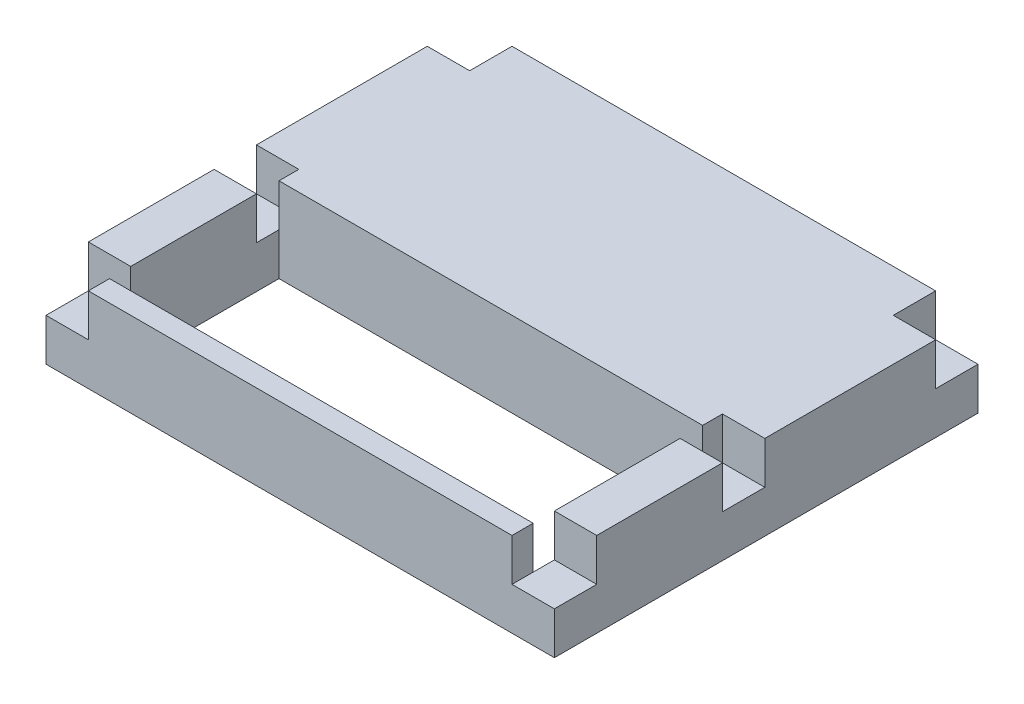
SolidWorks part; units mm, degrees
ref_plane "Front Plane" through (0, 0, 0) normal (0, 0, 1) x (1, 0, 0)
ref_plane "Top Plane" through (0, 0, 0) normal (0, 1, 0) x (1, 0, 0)
ref_plane "Right Plane" through (0, 0, 0) normal (1, 0, 0) x (0, 0, -1)
sketch "Sketch1" plane through (0, 0, 0) normal (0, 1, 0) x (1, 0, 0)
  line L1 (-60, 50) -> (60, 50)
  line L2 (-60, 50) -> (-60, -50)
  line L3 (-60, -50) -> (60, -50)
  line L4 (60, 50) -> (60, -50)
  line L5 (-60, 50) -> (60, -50) construction
  line L6 (-60, -50) -> (60, 50) construction
  point P0 (0, 0)
  dimension "D1" = 120
  dimension "D2" = 100
extrude "Boss-Extrude1" add sketch "Sketch1" along normal blind 20
sketch "Sketch5" plane through (0, 20, 0) normal (0, 1, 0) x (1, 0, 0)
  line L0 (-60, 50) -> (60, 50)
  line L1 (60, 50) -> (60, -50)
  line L2 (60, -50) -> (-60, -50)
  line L3 (-60, -50) -> (-60, 50)
  line L4 (-60, 0) -> (60, 0)
  line L5 (60, 0) -> (60, -50)
  line L6 (-60, 0) -> (-60, -50)
  line L7 (-60, 50) -> (-60, 0)
  line L8 (60, 50) -> (60, 0)
  line L9 (-60, 25) -> (-40, 25)
  line L10 (-40, 25) -> (-40, 30)
  line L11 (-40, 25) -> (-40, 20)
  line L12 (-40, 20) -> (-60, 20)
  line L13 (-40, 30) -> (-60, 30)
  line L14 (60, 30) -> (50, 30)
  line L15 (50, 30) -> (50, 20)
  line L16 (50, 20) -> (60, 20)
  line L17 (60, 20) -> (60, 30)
  line L18 (55, 20) -> (55, 25)
  line L19 (-60, 0) -> (-55, 0)
  line L20 (52, 28) -> (58, 28)
  line L21 (52, 28) -> (52, 22)
  line L22 (52, 22) -> (58, 22)
  line L23 (58, 28) -> (58, 22)
  line L24 (52, 28) -> (58, 22) construction
  line L25 (52, 22) -> (58, 28) construction
  line L26 (-53, 28) -> (-47, 28)
  line L27 (-53, 28) -> (-53, 22)
  line L28 (-53, 22) -> (-47, 22)
  line L29 (-47, 28) -> (-47, 22)
  line L30 (-53, 28) -> (-47, 22) construction
  line L31 (-53, 22) -> (-47, 28) construction
  line L32 (-55, 0) -> (-55, -5)
  line L33 (-55, -5) -> (-60, -5)
  line L34 (-60, -5) -> (-60, 0)
  line L35 (-60, -2.5) -> (-55, -2.5)
  line L36 (-60, -50) -> (-60, -45)
  line L37 (-60, -45) -> (-55, -45)
  line L38 (-55, -45) -> (-55, -50)
  line L39 (-55, -50) -> (-60, -50)
  line L40 (-60, -47.5) -> (-55, -47.5)
  line L41 (60, -50) -> (60, -45)
  line L42 (60, -45) -> (55, -45)
  line L43 (55, -45) -> (55, -50)
  line L44 (55, -50) -> (60, -50)
  line L45 (60, -47.5) -> (55, -47.5)
  line L46 (60, 0) -> (55, 0)
  line L47 (55, 0) -> (55, -5)
  line L48 (55, -5) -> (60, -5)
  line L49 (60, -5) -> (60, 0)
  line L50 (60, -2.5) -> (55, -2.5)
  line L52 (56, -1) -> (59, -1)
  line L53 (56, -1) -> (56, -4)
  line L54 (56, -4) -> (59, -4)
  line L55 (59, -1) -> (59, -4)
  line L56 (56, -1) -> (59, -4) construction
  line L57 (56, -4) -> (59, -1) construction
  line L58 (-59, -1) -> (-56, -1)
  line L59 (-59, -1) -> (-59, -4)
  line L60 (-59, -4) -> (-56, -4)
  line L61 (-56, -1) -> (-56, -4)
  line L62 (-59, -1) -> (-56, -4) construction
  line L63 (-59, -4) -> (-56, -1) construction
  line L64 (-59, -46) -> (-56, -46)
  line L65 (-59, -46) -> (-59, -49)
  line L66 (-59, -49) -> (-56, -49)
  line L67 (-56, -46) -> (-56, -49)
  line L68 (-59, -46) -> (-56, -49) construction
  line L69 (-59, -49) -> (-56, -46) construction
  line L70 (56, -46) -> (59, -46)
  line L71 (56, -46) -> (56, -49)
  line L72 (56, -49) -> (59, -49)
  line L73 (59, -46) -> (59, -49)
  line L74 (56, -46) -> (59, -49) construction
  line L75 (56, -49) -> (59, -46) construction
  point P26 (-50, 25)
  point P51 (57.5, -2.5)
  point P56 (-57.5, -2.5)
  point P61 (-57.5, -47.5)
  point P66 (57.5, -47.5)
  dimension "D1" = 6
  dimension "D2" = 6
  dimension "D3" = 10
  dimension "D4" = 10
  dimension "D5" = 5
  dimension "D6" = 6
  dimension "D7" = 6
  dimension "D8" = 3
  dimension "D9" = 3
  dimension "D10" = 5
  dimension "D11" = 5
  dimension "D12" = 5
  dimension "D13" = 5
  dimension "D14" = 3
  dimension "D15" = 3
  dimension "D16" = 3
  dimension "D17" = 5
  dimension "D18" = 5
  dimension "D19" = 3
  dimension "D20" = 5
  dimension "D21" = 5
  dimension "D22" = 3
  dimension "D23" = 3
sketch "Sketch6" plane through (0, 0, 0) normal (0, -1, 0) x (1, 0, 0)
  line L0 (-60, 50) -> (60, 50)
  line L1 (60, 50) -> (60, 0)
  line L2 (60, 0) -> (-60, 0)
  line L3 (-60, 0) -> (-60, 50)
  line L4 (-55, 5) -> (-55, 45)
  line L5 (-55, 45) -> (55, 45)
  line L6 (55, 45) -> (55, 5)
  line L7 (55, 5) -> (-55, 5)
  line L8 (-55, 45) -> (-50, 45)
  line L9 (-50, 45) -> (-50, 5)
  line L10 (-50, 5) -> (-55, 5)
  line L11 (-55, 45) -> (-55, 5)
  line L12 (-55, 45) -> (-50, 45)
  line L13 (55, 45) -> (50, 45)
  line L14 (50, 45) -> (50, 5)
  line L15 (50, 5) -> (55, 5)
  line L16 (55, 45) -> (55, 5)
  line L17 (50, 45) -> (55, 45)
  dimension "D1" = 5
extrude "Cut-Extrude1" cut sketch "Sketch6" against normal blind 20 contours L5 L6 L7 L4
sketch "Sketch7" plane through (60, 0, 0) normal (1, 0, 0) x (0, 0, -1)
  line L0 (50, 0) -> (-50, 0)
  line L1 (-50, 0) -> (-50, 20)
  line L2 (-50, 20) -> (50, 20)
  line L3 (50, 20) -> (50, 0)
  line L4 (-50, 20) -> (-50, 118.2899)
  line L5 (-50, 118.2899) -> (0, 118.2899)
  line L6 (0, 118.2899) -> (0, 20)
  line L7 (-50, 20) -> (0, 20)
  line L8 (0, 20) -> (-35.7746, 118.2899)
  line L9 (-17.8873, 69.1449) -> (-27.2842, 65.7247)
  line L10 (-27.2842, 65.7247) -> (-17.8873, 69.1449)
  line L11 (50, 118.2899) -> (50, 20)
  line L12 (-50, 20) -> (-45, 20)
  line L13 (-27.2842, 65.7247) -> (-46.4164, 118.2899)
  line L14 (-46.4164, 118.2899) -> (-10.6418, 20)
  line L15 (-45, 25) -> (-45, 114.3984)
  line L16 (-34.3582, 114.3984) -> (0, 114.3984)
  line L17 (-50, 20) -> (-50, 25)
  line L18 (-45, 25) -> (-12.4616, 25)
  line L19 (-1.8199, 25) -> (0, 25)
  line L20 (-45, 25) -> (-45, 20)
  line L21 (0, 118.2899) -> (50, 118.2899)
  line L22 (50, 118.2899) -> (50, 20)
  line L23 (0, 20) -> (0, 118.2899)
  line L24 (50, 20) -> (0, 20)
  line L25 (-17.8873, 69.1449) -> (-14.4671, 59.748)
  line L26 (-14.4671, 59.748) -> (35, 77.7526)
  line L27 (-17.8873, 69.1449) -> (-21.3075, 78.5419)
  line L28 (-21.3075, 78.5419) -> (35, 99.0361)
  line L31 (25, 20) -> (35, 20)
  line L32 (35, 20) -> (35, 118.2899)
  line L33 (25, 20) -> (15, 20)
  line L34 (15, 20) -> (15, 118.2899)
  line L35 (-10.6418, 20) -> (-1.2449, 23.4202)
  line L36 (-35.7746, 118.2899) -> (-45.1715, 114.8697)
  line L37 (-40.4731, 116.5798) -> (-5.9433, 21.7101)
  dimension "D1" = 70
sketch "Sketch13" plane through (-60, 0, 0) normal (-1, 0, 0) x (0, 0, 1)
  line L0 (-50, 20) -> (-50, 118.2899)
  line L1 (-50, 118.2899) -> (50, 118.2899)
  line L2 (50, 118.2899) -> (50, 20)
  line L3 (50, 20) -> (-50, 20)
  line L4 (-35, 118.2899) -> (-35, 20)
  line L5 (-35, 20) -> (-15, 20)
  line L6 (-15, 20) -> (-15, 118.2899)
  line L7 (46.4164, 118.2899) -> (10.6418, 20)
  line L8 (1.2449, 23.4202) -> (10.6418, 20)
  line L9 (0, 20) -> (35.7746, 118.2899)
  line L10 (35.7746, 118.2899) -> (45.1715, 114.8697)
  line L11 (40.4731, 116.5798) -> (5.9433, 21.7101)
  line L12 (12.4616, 25) -> (45, 25)
  line L13 (45, 25) -> (45, 114.3984)
  line L14 (0, 118.2899) -> (0, 20)
  line L15 (0, 25) -> (1.8199, 25)
  line L16 (-35, 99.0361) -> (21.3075, 78.5419)
  line L17 (-35, 77.7526) -> (14.4671, 59.748)
  line L18 (0, 114.3984) -> (34.3582, 114.3984)
extrude "Boss-Extrude4" add sketch "Sketch6<3>" against normal blind 20 contours L9 L5 L4 L7 | L5 L14 L7 L6 region at (-52.5, 0, 25) region at (52.5, 0, 25)
sketch "Sketch6<3>" plane through (0, 0, 0) normal (0, -1, 0) x (1, 0, 0) same geometry as "Sketch6"
sketch "Sketch14" plane through (0, 20, 0) normal (0, 1, 0) x (1, 0, 0)
  line L0 (60, 0) -> (60, -10.6418)
  line L1 (60, -10.6418) -> (50, -10.6418)
  line L2 (50, -45) -> (50, -5) construction
  line L3 (50, -10.6418) -> (50, 0)
  line L4 (50, 0) -> (60, 0)
  line L5 (55, -10.6418) -> (55, -5.3209)
  line L6 (55, -5.3209) -> (60, -5.3209)
  line L7 (60, -5.3209) -> (60, -10.3209)
  line L8 (0, 0) -> (0, 20.8987)
  line L9 (50, -0.3209) -> (60, -0.3209)
  line L10 (50, -0.3209) -> (50, -10.3209)
  line L11 (50, -10.3209) -> (60, -10.3209)
  line L12 (60, -0.3209) -> (60, -10.3209)
  line L13 (50, -0.3209) -> (60, -10.3209) construction
  line L14 (50, -10.3209) -> (60, -0.3209) construction
  line L15 (-50, -10.3209) -> (-60, -0.3209) construction
  line L16 (-50, -0.3209) -> (-60, -10.3209) construction
  line L17 (-60, -0.3209) -> (-60, -10.3209)
  line L18 (-50, -10.3209) -> (-60, -10.3209)
  line L19 (-50, -0.3209) -> (-50, -10.3209)
  line L20 (-50, -0.3209) -> (-60, -0.3209)
  line L21 (-60, -5.3209) -> (-60, -10.3209)
  line L22 (-55, -5.3209) -> (-60, -5.3209)
  line L23 (-55, -10.6418) -> (-55, -5.3209)
  line L24 (-50, 0) -> (-60, 0)
  line L25 (-50, -10.6418) -> (-50, 0)
  line L26 (-60, -10.6418) -> (-50, -10.6418)
  line L27 (-60, 0) -> (-60, -10.6418)
  line M3 (50, -5) -> (50, -45)
  line M5 (-50, -45) -> (-50, -5)
  line M8 (-60, 50) -> (-60, -50)
extrude "Cut-Extrude2" cut sketch "Sketch14" against normal blind 10 contours L18 L23 L22 L17 | L23 L18 L19 L20 L22 M5 M8 | L11 L5 L6 L0 L9 L3 M3 | L5 L11 L0 L6 region at (54.1667, 20, 4.4876) region at (57.5, 20, 7.8209) region at (-54.1667, 20, 4.4876) region at (-57.5, 20, 7.8209)
sketch "Sketch15" plane through (0, 20, 0) normal (0, 1, 0) x (1, 0, 0)
  line L0 (-60, 50) -> (-50, 50)
  line L1 (-60, 50) -> (60, 50) construction
  line L2 (-50, 50) -> (-50, 40)
  line L3 (-50, 40) -> (-60, 40)
  line L4 (-60, -50) -> (-60, 50) construction
  line L5 (-60, 40) -> (-60, 50)
  line L6 (60, 50) -> (60, 40)
  line L7 (60, 50) -> (60, -50) construction
  line L8 (60, 40) -> (50, 40)
  line L9 (50, 40) -> (50, 50)
  line L10 (50, 50) -> (60, 50)
  line L11 (60, -50) -> (50, -50)
  line L12 (60, -50) -> (-60, -50) construction
  line L13 (50, -50) -> (50, -40)
  line L14 (50, -45) -> (50, -10.3209) construction
  line L15 (50, -40) -> (60, -40)
  line L16 (60, -40) -> (60, -50)
  line L17 (-60, -50) -> (-60, -40)
  line L18 (-60, -40) -> (-50, -40)
  line L19 (-50, -45) -> (-50, -10.3209) construction
  line L20 (-50, -40) -> (-50, -50)
  line L21 (-50, -50) -> (-60, -50)
extrude "Cut-Extrude3" cut sketch "Sketch15" against normal blind 10
